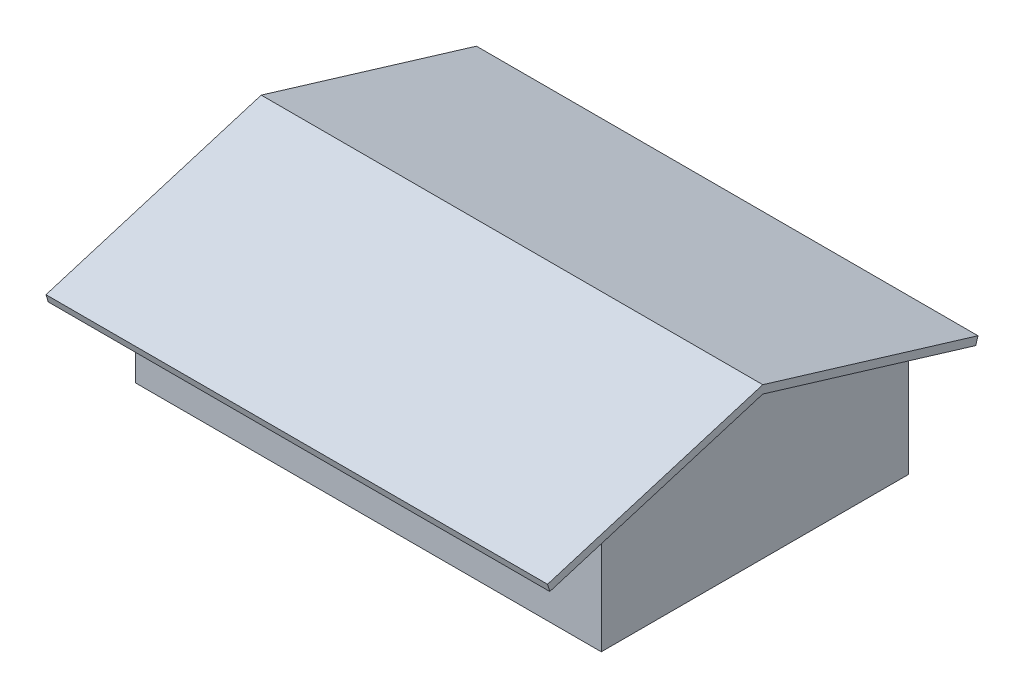
SolidWorks part; units mm, degrees
ref_plane "Front Plane" through (0, 0, 0) normal (0, 0, 1) x (1, 0, 0)
ref_plane "Top Plane" through (0, 0, 0) normal (0, 1, 0) x (1, 0, 0)
ref_plane "Right Plane" through (0, 0, 0) normal (1, 0, 0) x (0, 0, -1)
sketch "Sketch1" plane through (0, 0, 0) normal (1, 0, 0) x (0, 0, -1)
  line L0 (-5029.2, 0) -> (5029.2, 0)
  line L1 (5029.2, 0) -> (5029.2, 3392.194)
  line L2 (5029.2, 3657.6) -> (0, 5181.6)
  line L3 (0, 5181.6) -> (-5029.2, 3657.6)
  line L4 (-5029.2, 3392.194) -> (-5029.2, 0)
  line L5 (-5029.2, 3657.6) -> (-7040.88, 3048)
  line L6 (5029.2, 3657.6) -> (7040.88, 3048)
  line L7 (-5029.2, 3392.194) -> (-6967.2181, 2804.9158)
  line L9 (-7040.88, 3048) -> (-6967.2181, 2804.9158)
  line L10 (5029.2, 3392.194) -> (6967.2181, 2804.9158)
  line L12 (7040.88, 3048) -> (6967.2181, 2804.9158)
  line L14 (4955.5381, 3414.5158) -> (6967.2181, 2804.9158) construction
  line L15 (-4955.5381, 3414.5158) -> (-6967.2181, 2804.9158) construction
  point P4 (0, 0)
  dimension "D1" = 10058.4
  dimension "D2" = 3657.6
  dimension "D3" = 5181.6
  dimension "D4" = 3048
  dimension "D5" = 254
  dimension "D6" = 254
extrude "Boss-Extrude1" add sketch "Sketch1" along normal mid plane 15240
sketch "Sketch2" plane through (0, 0, 0) normal (1, 0, 0) x (0, 0, -1)
  line L0 (-6967.2181, 2804.9158) -> (-5029.2, 3392.194) construction
  line L1 (-7040.88, 3048) -> (-6967.2181, 2804.9158) construction
  line L2 (5029.2, 3392.194) -> (6967.2181, 2804.9158) construction
  line L3 (6967.2181, 2804.9158) -> (7040.88, 3048) construction
  line L4 (7040.88, 3048) -> (0, 5181.6) construction
  line L5 (0, 5181.6) -> (-7040.88, 3048) construction
  line L6 (-6967.2181, 2804.9158) -> (-5029.2, 3392.194)
  line L7 (-7040.88, 3048) -> (-6967.2181, 2804.9158)
  line L8 (5029.2, 3392.194) -> (6967.2181, 2804.9158)
  line L9 (6967.2181, 2804.9158) -> (7040.88, 3048)
  line L10 (7040.88, 3048) -> (0, 5181.6)
  line L11 (0, 5181.6) -> (-7040.88, 3048)
  line L12 (-5029.2, 3392.194) -> (0, 4916.194)
  line L13 (0, 4916.194) -> (5029.2, 3392.194)
extrude "Boss-Extrude2" add sketch "Sketch2" along normal blind 254 from surface starting at face at (7620, 2630.2022, 0)
extrude "Boss-Extrude3" add sketch "Sketch2<2>" against normal blind 914.4 from surface starting at face at (-7620, 2630.2022, 0)
sketch "Sketch2<2>" plane through (0, 0, 0) normal (1, 0, 0) x (0, 0, -1) same geometry as "Sketch2"
